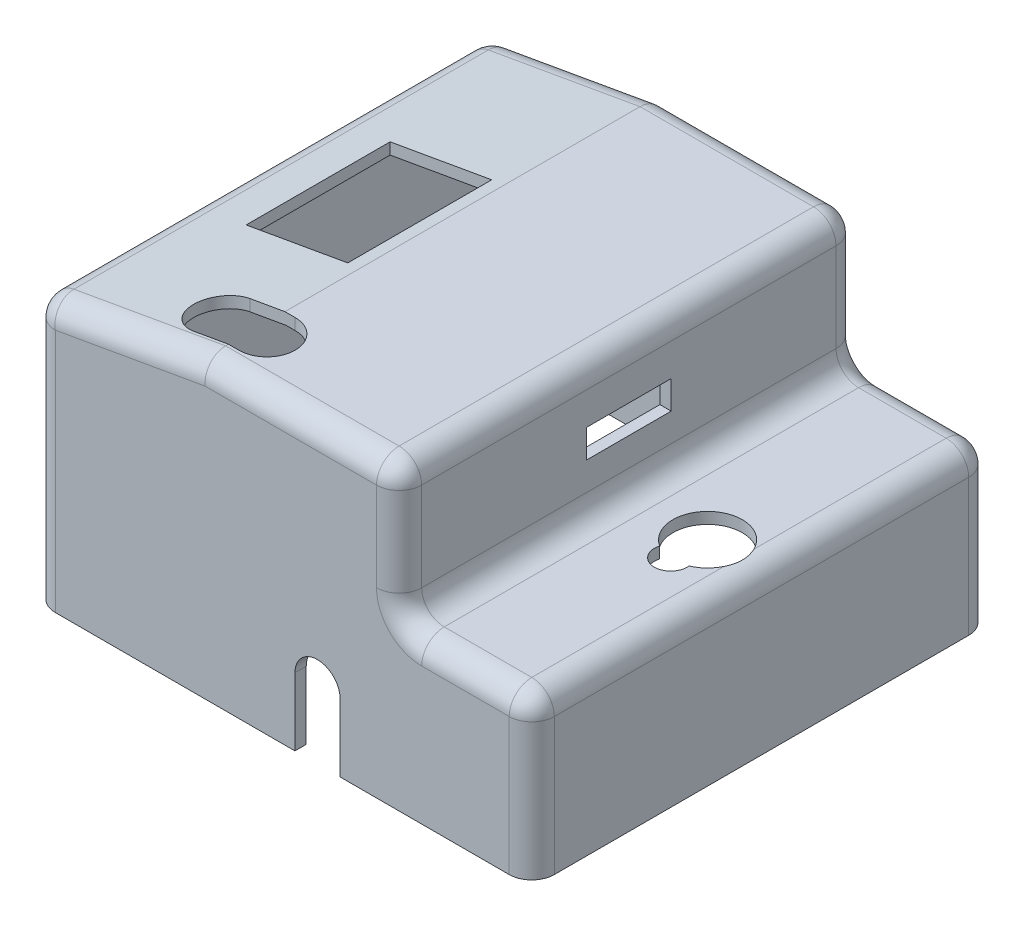
SolidWorks part; units mm, degrees
ref_plane "Přední rovina" through (0, 0, 0) normal (0, 0, 1) x (1, 0, 0)
ref_plane "Horní rovina" through (0, 0, 0) normal (0, 1, 0) x (1, 0, 0)
ref_plane "Pravá rovina" through (0, 0, 0) normal (1, 0, 0) x (0, 0, -1)
sketch "Sketch1" plane through (0, 0, 0) normal (0, 0, 1) x (1, 0, 0)
  line L0 (-42.2, 0) -> (42.2, 0)
  line L4 (-42.2, 0) -> (-42.2, 50)
  line L7 (42.2, 26.25) -> (18.7, 26.25) construction
  line L11 (18.7, 26.25) -> (42.2, 26.25)
  line L12 (42.2, 26.25) -> (42.2, 0)
  line L17 (18.7, 26.25) -> (18.7, 50)
  line L18 (18.7, 50) -> (-42.2, 50)
  dimension "D1" = 84.4
  dimension "D4" = 26.25
  dimension "D5" = 23.5
  dimension "D9" = 50
extrude "Boss-Extrude1" add sketch "Sketch1" along normal blind 38.7 and the other way blind 38.7
chamfer "Chamfer1" distance 5 angle 80 1 edges at (-42.2, 50, 0) first distance on face at (-42.2, 25, 0)
shell "Shell1" thickness 2 removed face at (0, 0, 0) outward yes
fillet "Fillet2" radius 4 16 edges at (-44.2, 23.3391, -40.7) (-44.2, 23.3391, 40.7) (32.45, 28.25, -40.7) (32.45, 28.25, 40.7) (20.7, 40.125, -40.7) (20.7, 40.125, 40.7) (44.2, 28.25, 0) (20.7, 28.25, 0) (3.3407, 52, -40.7) (20.7, 52, 0) (3.3407, 52, 40.7) (44.2, 14.125, 40.7) (44.2, 14.125, -40.7) (-29.1093, 49.3391, 40.7) (-29.1093, 49.3391, -40.7) (-44.2, 46.6782, 0)
sketch "Sketch2" plane through (0, 0, 0) normal (0, -1, 0) x (1, 0, 0)
  line L0 (42.2, -36.2) -> (36.2, -30.2) construction
  line L1 (42.2, -36.2) -> (36.2, -36.2)
  line L2 (42.2, -36.2) -> (42.2, -30.2)
  line L3 (42.2, -30.2) -> (36.2, -30.2)
  line L4 (36.2, -36.2) -> (36.2, -30.2)
  line L5 (42.2, -38.7) -> (42.2, 38.7) construction
  line L6 (-42.2, -38.7) -> (42.2, -38.7) construction
  line L8 (36.2, -36.2) -> (42.2, -36.2)
  line L9 (36.2, -36.2) -> (36.2, -38.7)
  line L10 (36.2, -38.7) -> (42.2, -38.7)
  line L11 (42.2, -36.2) -> (42.2, -38.7)
  circle A0 centre (39.2, -33.2) radius 1.45
  line M4 (42.2, -38.7) -> (-42.2, -38.7)
  line M18 (42.2, 38.7) -> (42.2, -38.7)
  dimension "D3" = 2.9
  dimension "D1" = 6
  dimension "D2" = 6
  dimension "D4" = 2.5
extrude "Boss-Extrude2" add sketch "Sketch2" against normal blind 4 from offset 1.5 contours L1 L9 M4 M18 | L1 L0 A0 L4 | L0 L3 A0 M18 region at (38.0731, 0, -34.3269) region at (39.2, 0, -37.45) region at (40.3269, 0, -32.0731) offset against normal yes
mirror "Mirror1" about plane through (0, 0, 0) normal (0, 0, 1) of "Boss-Extrude2"
fillet "Fillet3" radius 2 6 edges at (36.2, 3.5, 38.7) (36.2, 3.5, 30.2) (36.2, 3.5, -38.7) (36.2, 3.5, -30.2) (42.2, 3.5, -30.2) (42.2, 3.5, 30.2)
sketch "Sketch3" plane through (0, 28.25, 0) normal (0, 1, 0) x (1, 0, 0)
  line L1 (44.2, 36.7) -> (44.2, -36.7) construction
  circle A0 centre (34.65, 0) radius 6.15
  circle A1 centre (34.1517, -6.0294) radius 2.9
  dimension "D1" = 12.3
  dimension "D2" = 5.8
  dimension "D3" = 6.05
  dimension "D4" = 9.55
extrude "Cut-Extrude1" cut sketch "Sketch3" against normal up to next contours A1 A0 | A0 A1 | A0 A1 | A0 region at (34.6959, 28.25, -0.5548) region at (34.2581, 28.25, 4.7416) region at (34.0569, 28.25, 7.1765)
sketch "Sketch4" plane through (0, 0, 0) normal (0, -1, 0) x (1, 0, 0)
  line L0 (-42.2, -38.7) -> (-42.2, 38.7) construction
  line L1 (-42.2, -10) -> (-37.2, -10)
  line L2 (-42.2, -10) -> (-42.2, 10)
  line L3 (-42.2, 10) -> (-37.2, 10)
  line L4 (-37.2, -10) -> (-37.2, 10)
  line L5 (-42.2, -10) -> (-37.2, 10) construction
  line L6 (-42.2, 10) -> (-37.2, -10) construction
  point P0 (-39.7, 0)
  dimension "D1" = 5
  dimension "D2" = 20
extrude "Boss-Extrude3" add sketch "Sketch4" against normal blind 2 from offset 1.5 offset against normal yes
fillet "Fillet4" radius 2 3 edges at (-42.2, 3.5, 0) (-42.2, 2.5, 10) (-42.2, 2.5, -10)
sketch "Sketch5" plane through (20.7, 0, 0) normal (1, 0, 0) x (0, 0, -1)
  line L1 (-7.5, 42.25) -> (7.5, 42.25)
  line L2 (-7.5, 42.25) -> (-7.5, 37.25)
  line L3 (-7.5, 37.25) -> (7.5, 37.25)
  line L4 (7.5, 42.25) -> (7.5, 37.25)
  line L5 (-7.5, 42.25) -> (7.5, 37.25) construction
  line L6 (-7.5, 37.25) -> (7.5, 42.25) construction
  line L7 (-36.7, 32.25) -> (36.7, 32.25) construction
  point P0 (0, 39.75)
  dimension "D1" = 5
  dimension "D2" = 15
  dimension "D3" = 5
extrude "Cut-Extrude2" cut sketch "Sketch5" against normal up to next
sketch "Sketch6" plane through (0, 0, 40.7) normal (0, 0, 1) x (1, 0, 0)
  line L0 (6.25, 0) -> (6.25, 12) construction
  line L1 (-40.2, 0) -> (40.2, 0) construction
  line L2 (2.25, 0) -> (2.25, 12)
  line L3 (10.25, 0) -> (10.25, 12)
  line L4 (-44.2, 0) -> (-44.2, 43.3218) construction
  arc A0 (2.25, 0) -> (10.25, 0) centre (6.25, 0) ccw
  arc A1 (10.25, 12) -> (2.25, 12) centre (6.25, 12) ccw
  point P4 (6.25, 6)
  dimension "D1" = 50.45
  dimension "D2" = 8
  dimension "D3" = 12
extrude "Cut-Extrude3" cut sketch "Sketch6" against normal through all
sketch "Sketch7" plane through (-18.1503, 52, 0) normal (0, 1, 0) x (1, 0, 0)
  line L0 (-26.0497, -36.7) -> (-26.0497, 36.7) construction
  line L1 (1.8085, 12.75) -> (-16.1915, 12.75)
  line L2 (1.8085, 12.75) -> (1.8085, -12.75)
  line L3 (1.8085, -12.75) -> (-16.1915, -12.75)
  line L4 (-16.1915, 12.75) -> (-16.1915, -12.75)
  line L5 (1.8085, 12.75) -> (-16.1915, -12.75) construction
  line L6 (1.8085, -12.75) -> (-16.1915, 12.75) construction
  point P0 (-7.1915, 0)
  dimension "D1" = 18
  dimension "D2" = 25.5
  dimension "D4" = 18.8582
extrude "Cut-Extrude4" cut sketch "Sketch7" against normal up to next
sketch "Sketch8" plane through (0, 52, 0) normal (0, 1, 0) x (1, 0, 0)
  line L0 (-12.2, -31.2) -> (-20.2, -31.2) construction
  line L1 (-12.2, -36.2) -> (-20.2, -36.2)
  line L3 (-12.2, -26.2) -> (-20.2, -26.2)
  line L4 (-40.8946, -36.7) -> (-14.0186, -36.7) construction
  line L5 (-40.8946, 36.7) -> (-40.8946, -36.7) construction
  arc A1 (-12.2, -36.2) -> (-12.2, -26.2) centre (-12.2, -31.2) ccw
  arc A2 (-20.2, -26.2) -> (-20.2, -36.2) centre (-20.2, -31.2) ccw
  point P7 (-16.2, -31.2)
  point P12 (0, 0)
  point P13 (0, 0)
  point P14 (-32.3518, -55.2158)
  dimension "D1" = 5.5
  dimension "D2" = 24.6946
  dimension "D4" = 5
  dimension "D5" = 8
extrude "Cut-Extrude5" cut sketch "Sketch8" against normal up to next
sketch "Sketch10" plane through (0, 0, -40.7) normal (0, 0, -1) x (-1, 0, 0)
  line L0 (40.2, 0) -> (-2.25, 0) construction
  line L1 (11.7, 38.5) -> (24.7, 38.5)
  line L2 (11.7, 38.5) -> (11.7, 30.5)
  line L3 (11.7, 30.5) -> (24.7, 30.5)
  line L4 (24.7, 38.5) -> (24.7, 30.5)
  line L5 (11.7, 38.5) -> (24.7, 30.5) construction
  line L6 (11.7, 30.5) -> (24.7, 38.5) construction
  point P0 (18.2, 34.5)
  dimension "D1" = 13
  dimension "D2" = 8
  dimension "D3" = 34.5
  dimension "D4" = 24
extrude "Cut-Extrude6" cut sketch "Sketch10" against normal up to next
fillet "Fillet5" radius 2 4 edges at (-24.7, 30.5, -39.7) (-11.7, 30.5, -39.7) (-11.7, 38.5, -39.7) (-24.7, 38.5, -39.7)
